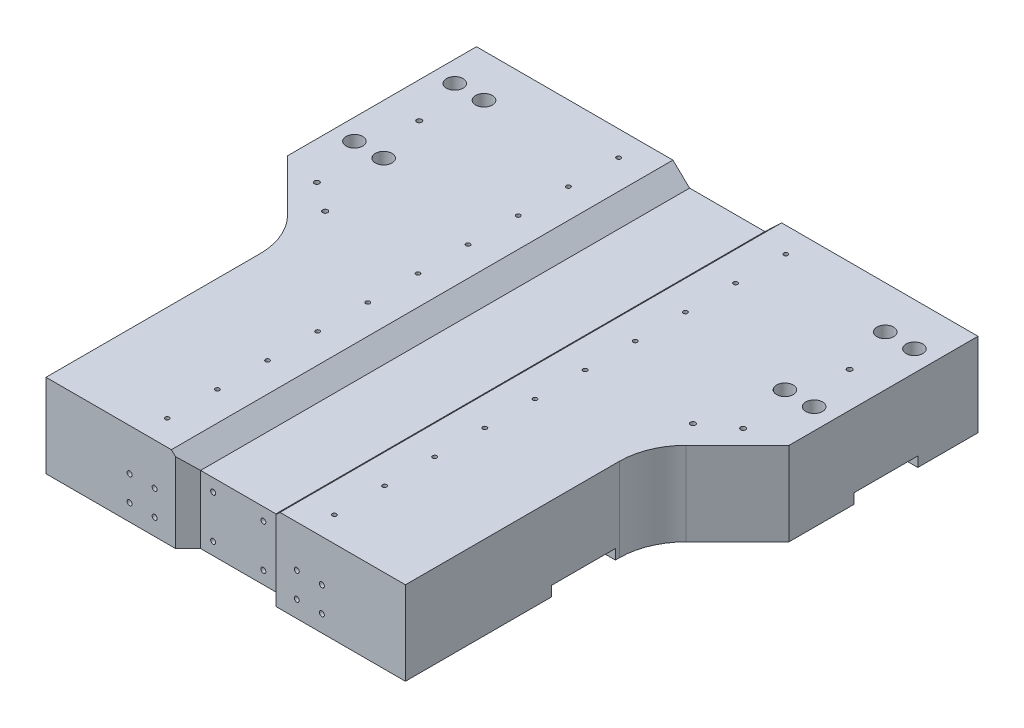
SolidWorks part; units mm, degrees
ref_plane "Front Plane" through (0, 0, 0) normal (0, 0, 1) x (1, 0, 0)
ref_plane "Top Plane" through (0, 0, 0) normal (0, 1, 0) x (1, 0, 0)
ref_plane "Right Plane" through (0, 0, 0) normal (1, 0, 0) x (0, 0, -1)
sketch "Sketch1" plane through (0, 0, 0) normal (0, 1, 0) x (1, 0, 0)
  line L1 (-300, 300) -> (300, 300)
  line L2 (-300, 300) -> (-300, -300)
  line L3 (-300, -300) -> (300, -300)
  line L4 (300, 300) -> (300, -300)
  line L5 (0, -300) -> (0, 300) construction
  line L6 (-300, 0) -> (300, 0) construction
  point P0 (0, 0)
  dimension "D1" = 600
extrude "Boss-Extrude1" add sketch "Sketch1" along normal blind 100
sketch "Sketch2" plane through (0, 100, 0) normal (0, 1, 0) x (1, 0, 0)
  line L0 (-300, -300) -> (-220, -300)
  line L9 (-300, -300) -> (300, -300) construction
  line L11 (300, -300) -> (220, -300)
  line L13 (-300, 300) -> (-300, -300) construction
  line L15 (-300, -300) -> (-300, 60)
  line L16 (300, -300) -> (300, 60)
  line L38 (-300, 60) -> (-300, 74)
  line L41 (300, 60) -> (300, 74)
  line L45 (-220, 74) -> (-300, 74)
  line L48 (220, 74) -> (300, 74)
  line L49 (-220, 74) -> (-215, 74)
  line L50 (-215, 74) -> (-215, -300)
  line L51 (-215, -300) -> (-220, -300)
  line L52 (220, 74) -> (215, 74)
  line L53 (215, 74) -> (215, -300)
  line L54 (215, -300) -> (220, -300)
extrude "Cut-Extrude1" cut sketch "Sketch2" against normal through all
chamfer "Chamfer5" distance 85 angle 45 2 edges at (-215, 50, -74) (215, 50, -74)
sketch "Sketch3" plane through (0, 0, 300) normal (0, 0, 1) x (1, 0, 0)
  line L0 (-35, 81) -> (-45, 81)
  line L2 (35, 81) -> (45, 81)
  line L4 (0, 81) -> (35, 81)
  line L8 (0, 81) -> (-35, 81)
  line L10 (-45, 100) -> (45, 100)
  line L13 (-215, 100) -> (215, 100) construction
  line L14 (-65, 100) -> (-45, 100)
  line L17 (45, 100) -> (65, 100)
  line L22 (-45, 81) -> (-65, 100)
  line L23 (45, 81) -> (65, 100)
extrude "Cut-Extrude2" cut sketch "Sketch3" against normal through all
sketch "Sketch9" plane through (0, 100, 0) normal (0, 1, 0) x (1, 0, 0)
  circle A0 centre (275, 129) radius 10
  circle A1 centre (240, 129) radius 10
  circle A3 centre (240, 249) radius 10
  circle A5 centre (275, 249) radius 10
  circle A6 centre (-275, 129) radius 10
  circle A7 centre (-240, 249) radius 10
  circle A8 centre (-275, 249) radius 10
  circle A11 centre (-240, 129) radius 10
  circle A12 centre (240, 189) radius 10 [skipped]
  circle A13 centre (275, 189) radius 10 [skipped]
  dimension "D1" = 2
  dimension "D2" = 3
extrude "Cut-Extrude5" cut sketch "Sketch9" against normal through all
sketch "Sketch12" plane through (0, 100, 0) normal (0, 1, 0) x (1, 0, 0)
  circle A40 centre (-100, -270) radius 2.5
  circle A41 centre (100, -270) radius 2.5
  circle A42 centre (100, -210) radius 2.5
  circle A43 centre (100, -150) radius 2.5
  circle A44 centre (100, -90) radius 2.5
  circle A45 centre (100, -30) radius 2.5
  circle A46 centre (100, 30) radius 2.5
  circle A47 centre (100, 90) radius 2.5
  circle A48 centre (100, 150) radius 2.5
  circle A49 centre (100, 210) radius 2.5
  circle A50 centre (100, 270) radius 2.5
  circle A61 centre (-100, -210) radius 2.5
  circle A62 centre (-100, -150) radius 2.5
  circle A63 centre (-100, -90) radius 2.5
  circle A64 centre (-100, -30) radius 2.5
  circle A65 centre (-100, 30) radius 2.5
  circle A66 centre (-100, 90) radius 2.5
  circle A67 centre (-100, 150) radius 2.5
  circle A68 centre (-100, 210) radius 2.5
  circle A69 centre (-100, 270) radius 2.5
  dimension "D1" = 2
  dimension "D2" = 10
extrude "Cut-Extrude7" cut sketch "Sketch12" against normal blind 30
sketch "Sketch14" plane through (0, 81, 0) normal (0, 1, 0) x (1, 0, 0)
  line L5 (-45, -300) -> (45, -300)
  line L6 (-45, -300) -> (-45, -285)
  line L11 (45, -285) -> (45, -300)
  line L15 (-45, -285) -> (45, -285)
extrude "Cut-Extrude8" cut sketch "Sketch14" against normal through all
chamfer "Chamfer3" distance 15 angle 45 2 edges at (45, 40.5, 300) (-45, 40.5, 300)
sketch "Sketch15" plane through (-300, 0, 0) normal (-1, 0, 0) x (0, 0, 1)
  line L0 (125, -0.7) -> (125, 12) construction
  line L1 (125, 12) -> (48.8, 12) construction
  line L2 (48.8, 12) -> (48.8, -0.7) construction
  line L3 (48.8, -0.7) -> (125, -0.7) construction
  line L4 (-228, 12) -> (-228, -0.7) construction
  line L5 (-228, -0.7) -> (-151.8, -0.7) construction
  line L6 (-151.8, -0.7) -> (-151.8, 12) construction
  line L7 (-151.8, 12) -> (-228, 12) construction
  line L8 (125, -0.7) -> (125, 12)
  line L9 (125, 12) -> (48.8, 12)
  line L10 (48.8, 12) -> (48.8, -0.7)
  line L11 (48.8, -0.7) -> (125, -0.7)
  line L12 (-228, 12) -> (-228, -0.7)
  line L13 (-228, -0.7) -> (-151.8, -0.7)
  line L14 (-151.8, -0.7) -> (-151.8, 12)
  line L15 (-151.8, 12) -> (-228, 12)
extrude "Cut-Extrude9" cut sketch "Sketch15" against normal through all
sketch "Sketch22" plane through (0, 0, -300) normal (0, 0, -1) x (-1, 0, 0)
  line L0 (-45, 81) -> (-45, 0)
  line L1 (-300, 0) -> (300, 0) construction
  line L2 (-45, 0) -> (45, 0)
  line L3 (45, 0) -> (45, 81)
  line L4 (45, 81) -> (-45, 81)
sketch "Sketch17" plane through (0, 0, 285) normal (0, 0, 1) x (1, 0, 0)
  line L8 (30, 66) -> (-30, 66)
  line L9 (-30, 66) -> (-30, 15)
  line L10 (-30, 15) -> (30, 15)
  line L11 (30, 15) -> (30, 66)
  line L12 (30, 66) -> (-30, 66)
  line L13 (-30, 66) -> (-30, 15)
  line L14 (-30, 15) -> (30, 15)
  line L15 (30, 15) -> (30, 66)
  dimension "D1" = 15
sketch "Sketch19" plane through (0, 0, -300) normal (0, 0, -1) x (-1, 0, 0)
  line L0 (30, 66) -> (30, 15) construction
  line L1 (30, 15) -> (-30, 15) construction
  line L2 (-30, 15) -> (-30, 66) construction
  line L3 (-30, 66) -> (30, 66) construction
  line L4 (30, 66) -> (30, 15)
  line L5 (30, 15) -> (-30, 15)
  line L6 (-30, 15) -> (-30, 66)
  line L7 (-30, 66) -> (30, 66)
sketch "Sketch20" plane through (0, 0, 300) normal (0, 0, 1) x (1, 0, 0)
  line L2 (85, 100) -> (85, 50)
  line L3 (-85, 0) -> (-85, 20)
  line L4 (-215, 100) -> (-65, 100) construction
  line L5 (-85, 100) -> (-85, 50)
  line L6 (115, 100) -> (115, 50)
  line L7 (-115, 100) -> (-115, 50)
  line L8 (0, 34.1921) -> (0, 91.6213)
  line L9 (-215, 0) -> (-60, 0) construction
  line L10 (-115, 0) -> (-115, 20)
  line L11 (85, 0) -> (85, 20)
  line L12 (115, 0) -> (115, 20)
sketch "Sketch21" plane through (0, 0, -300) normal (0, 0, -1) x (-1, 0, 0)
  line L4 (-115, 100) -> (-115, 80)
  line L5 (-85, 100) -> (-85, 80)
  line L6 (85, 100) -> (85, 80)
  line L7 (115, 100) -> (115, 80)
  line L8 (115, 0) -> (115, 20) construction
  line L9 (85, 0) -> (85, 20) construction
  line L10 (-85, 0) -> (-85, 20) construction
  line L11 (-115, 0) -> (-115, 20) construction
  line L12 (115, 0) -> (115, 20)
  line L13 (85, 0) -> (85, 20)
  line L14 (-85, 0) -> (-85, 20)
  line L15 (-115, 0) -> (-115, 20)
hole_wizard "Ø6.0mm Dowel Hole1" positions "3DSketch2" profile "Sketch18" hole size "Ø6.0" standard "ANSI Metric"
sketch3d "3DSketch2"
  point P0 (-30, 66, 285)
  point P3 (30, 66, 285)
  point P6 (30, 15, 285)
  point P9 (-30, 15, 285)
  point P13 (30, 66, -300)
  point P16 (-30, 66, -300)
  point P19 (-30, 15, -300)
  point P22 (30, 15, -300)
  point P26 (-85, 50, 300)
  point P29 (-115, 50, 300)
  point P32 (85, 50, 300)
  point P35 (115, 50, 300)
  point P38 (-115, 80, -300)
  point P41 (-85, 80, -300)
  point P44 (85, 80, -300)
  point P47 (115, 80, -300)
  point P50 (-115, 20, 300)
  point P53 (-85, 20, 300)
  point P56 (85, 20, 300)
  point P59 (115, 20, 300)
  point P62 (-115, 20, -300)
  point P65 (-85, 20, -300)
  point P68 (85, 20, -300)
  point P71 (115, 20, -300)
sketch "Sketch18" plane through (-30, 66, 285) normal (1, 0, 0) x (0, -1, 0)
  line L0 (0, 0) -> (0, 31.8026)
  line L1 (0, 31.8026) -> (3, 30)
  line L2 (3, 30) -> (3, 0)
  line L5 (3, 0) -> (0, 0)
  line L10 (0, 31.8026) -> (-3, 30) construction
  line L11 (0, -6.35) -> (0, 107.95) construction
  dimension "Hole Dia." = 6
  dimension "Hole Depth" = 30
  dimension "Drill Angle" = 118
sketch "Sketch23" plane through (0, 100, 0) normal (0, 1, 0) x (1, 0, 0)
  circle A0 centre (-257.5, 189) radius 3
  circle A1 centre (257.5, 189) radius 3
extrude "Cut-Extrude10" cut sketch "Sketch23" against normal through all
sketch "Sketch24" plane through (0, 100, 0) normal (0, 1, 0) x (1, 0, 0)
  line L0 (210, 74) -> (300, 74) construction
  line L1 (210, 74) -> (300, 74)
  line L2 (210, 74) -> (210, 4)
  line L3 (210, 39) -> (220, 39)
  line L4 (255, 74) -> (255, 64)
  line L5 (0, 0) -> (0, -82.778)
  circle A0 centre (255, 64) radius 3
  circle A1 centre (220, 39) radius 3
  circle A2 centre (-220, 39) radius 3
  circle A3 centre (-255, 64) radius 3
extrude "Cut-Extrude11" cut sketch "Sketch24" against normal blind 20 contours A3 | A2 | A0 | A1
fillet "Fillet1" radius 80 2 edges at (215, 50, 11) (-215, 50, 11)
